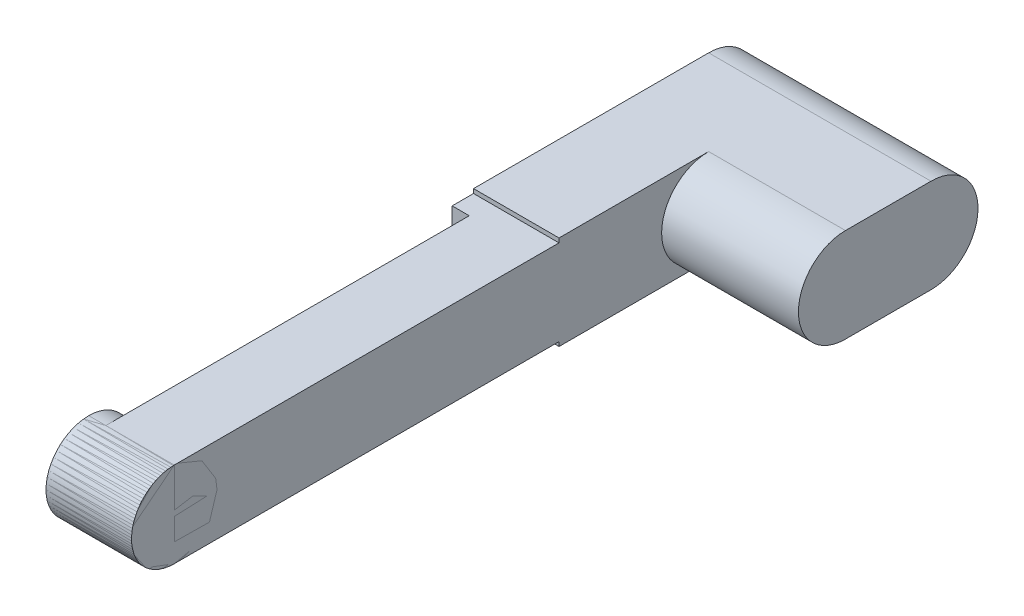
SolidWorks part; units mm, degrees
material "201 Annealed Stainless Steel (SS)"
ref_plane "Front Plane" through (0, 0, 0) normal (0, 0, 1) x (1, 0, 0)
ref_plane "Top Plane" through (0, 0, 0) normal (0, 1, 0) x (1, 0, 0)
ref_plane "Right Plane" through (0, 0, 0) normal (1, 0, 0) x (0, 0, -1)
sketch "Sketch1" plane through (0, 0, 0) normal (1, 0, 0) x (0, 0, -1)
  line L0 (0, 0) -> (-500, 0) construction
  line L5 (-500, 50) -> (-50, 50)
  line L6 (50, -55) -> (-50, -55)
  line L7 (50, -55) -> (50, 55)
  line L8 (50, 55) -> (-50, 55)
  line L9 (-50, -55) -> (-50, 55)
  line L10 (50, -55) -> (-50, 55) construction
  line L11 (50, 55) -> (-50, -55) construction
  line L12 (-500, -50) -> (-50, -50)
  line L13 (0, 0) -> (280, 0)
  line L15 (280, 0) -> (50, 0)
  line L16 (280, 0) -> (280, 55)
  line L17 (280, 55) -> (50, 55)
  line L18 (50, 0) -> (50, 55)
  line L19 (280, 0) -> (50, 0)
  line L20 (280, 0) -> (280, -55)
  line L21 (280, -55) -> (50, -55)
  line L22 (50, 0) -> (50, -55)
  circle A0 centre (-500, 0) radius 50
  dimension "D1" = 100
  dimension "D2" = 110
  dimension "D3" = 100
  dimension "D4" = 500
  dimension "D5" = 280
extrude "Boss-Extrude1" add sketch "Sketch1" along normal blind 100 contours A0 L9 | A0 | L9 L6 L7 L8 | L21 L20 L13 L7 | L16 L17 L7 L13 region at (0, 0, 255.5167) region at (0, 0, 500) region at (0, 52.5, 48.5134) region at (0, 27.5, -165) region at (0, -27.5, -165)
sketch "Sketch2" plane through (0, 55, 0) normal (0, 1, 0) x (1, 0, 0)
  line L0 (0, 280) -> (260, 280)
  line L1 (260, 280) -> (260, 70)
  line L2 (260, 70) -> (100, 70)
  line L4 (0, 280) -> (0, -50)
  line L5 (0, -50) -> (100, -50)
  line L6 (100, -50) -> (100, 280)
  line L7 (100, 280) -> (0, 280)
  line L8 (0, 280) -> (0, -50)
  line L10 (100, -50) -> (100, 280)
  line L11 (100, 280) -> (0, 280)
  line L15 (0, -50) -> (100, -50)
  line M9 (100, -50) -> (100, 280)
  dimension "D2" = 260
  dimension "D3" = 210
  dimension "D1" = 0
extrude "Boss-Extrude2" add sketch "Sketch2" against normal up to surface (110 mm away) contours L2 L1 L0 M9 region at (180, 55, -175) up to face at (50, -55, -115)
sketch "Sketch3" plane through (260, 0, 0) normal (1, 0, 0) x (0, 0, -1)
  line L4 (70, -55) -> (280, -55)
  line L5 (280, -55) -> (280, 55)
  line L6 (280, 55) -> (70, 55)
  line L7 (70, 55) -> (70, -55)
  line L8 (70, -55) -> (280, -55)
  line L9 (280, -55) -> (280, 55)
  line L10 (280, 55) -> (70, 55)
  line L11 (70, 55) -> (70, -55)
  circle A0 centre (125, 0) radius 55
  circle A1 centre (225, 0) radius 55
  line M5 (70, -55) -> (280, -55)
  line M6 (280, -55) -> (280, 55)
  line M7 (280, 55) -> (70, 55)
  line M8 (70, 55) -> (70, -55)
  dimension "D1" = 0
extrude "Cut-Extrude1" cut sketch "Sketch3" against normal up to surface (260 mm away) contours A1 L9 M7 | A1 M5 M6 region at (260, -42.7148, -267.7148) region at (260, 42.7148, -267.7148) up to face at (0, 0, 86.25)
extrude "Cut-Extrude2" cut sketch "Sketch3<3>" against normal up to surface (160 mm away) contours A0 L10 M8 | A0 L11 M5 region at (260, -42.7148, -82.2852) region at (260, 42.7148, -82.2852) up to face at (100, 0, 138.75)
sketch "Sketch3<3>" plane through (260, 0, 0) normal (1, 0, 0) x (0, 0, -1) same geometry as "Sketch3"
sketch "Sketch5" plane through (0, 55, 0) normal (0, 1, 0) x (1, 0, 0)
  line L0 (0, 0) -> (0, -75)
  line L1 (0, -75) -> (20, -75)
  line L2 (20, -75) -> (20, -500)
  line L6 (100, -50) -> (100, 125)
  line L7 (100, 125) -> (260, 125)
  line L8 (260, 125) -> (260, 225)
  line L9 (260, 225) -> (0, 225)
  line L10 (0, 225) -> (0, -50)
  line L11 (0, -50) -> (100, -50)
  line L12 (100, -50) -> (100, 125)
  line L13 (100, 125) -> (260, 125)
  line L14 (260, 125) -> (260, 225)
  line L15 (260, 225) -> (0, 225)
  line L16 (0, 225) -> (0, -50)
  line L21 (0, -50) -> (100, -50)
  dimension "D2" = 75
  dimension "D3" = 20
  dimension "D1" = 0
extrude "Boss-Extrude3" add sketch "Sketch1<3>" along normal blind 100 separate body contours A0 region at (0, 0, 500)
sketch "Sketch1<3>" plane through (0, 0, 0) normal (1, 0, 0) x (0, 0, -1) same geometry as "Sketch1"
sketch "Sketch6" plane through (0, 50, 0) normal (0, 1, 0) x (1, 0, 0)
  line L0 (0, -50) -> (0, -75)
  line L1 (0, -75) -> (20, -75)
  line L2 (20, -75) -> (20, -500)
  line L4 (0, -50) -> (0, -500)
  line L5 (0, -500) -> (100, -500)
  line L6 (100, -500) -> (100, -50)
  line L7 (100, -50) -> (0, -50)
  line L8 (0, -50) -> (0, -500)
  line L9 (0, -500) -> (100, -500)
  line L10 (100, -500) -> (100, -50)
  line L11 (100, -50) -> (0, -50)
  line M7 (0, -50) -> (0, -500)
  line M8 (0, -500) -> (100, -500)
  dimension "D2" = 25
  dimension "D3" = 20
  dimension "D1" = 0
extrude "Cut-Extrude4" cut sketch "Sketch6" against normal blind 100 contours L2 L1 M7 M8 region at (10, 50, 287.5)
sketch "Sketch7" plane through (20, 0, 0) normal (-1, 0, 0) x (0, 0, 1)
  line L1 (500, -50) -> (500, 50)
  line L2 (500, -50) -> (500, 50)
  arc A1 (500, 50) -> (500, -50) centre (500, 0) ccw
  arc A2 (500, 50) -> (500, -50) centre (500, 0) ccw
  dimension "D1" = 0
extrude "Boss-Extrude4" add sketch "Sketch7" along normal up to surface (20 mm away) separate body up to face at (0, 0, 525)
ref_plane "Plane1" through (-27.37, 0, 0) normal (-1, 0, 0) x (0, 0, 1)
sketch "Sketch11" plane through (-27.37, 0, 0) normal (-1, 0, 0) x (0, 0, 1)
  point P0 (0, 0)
